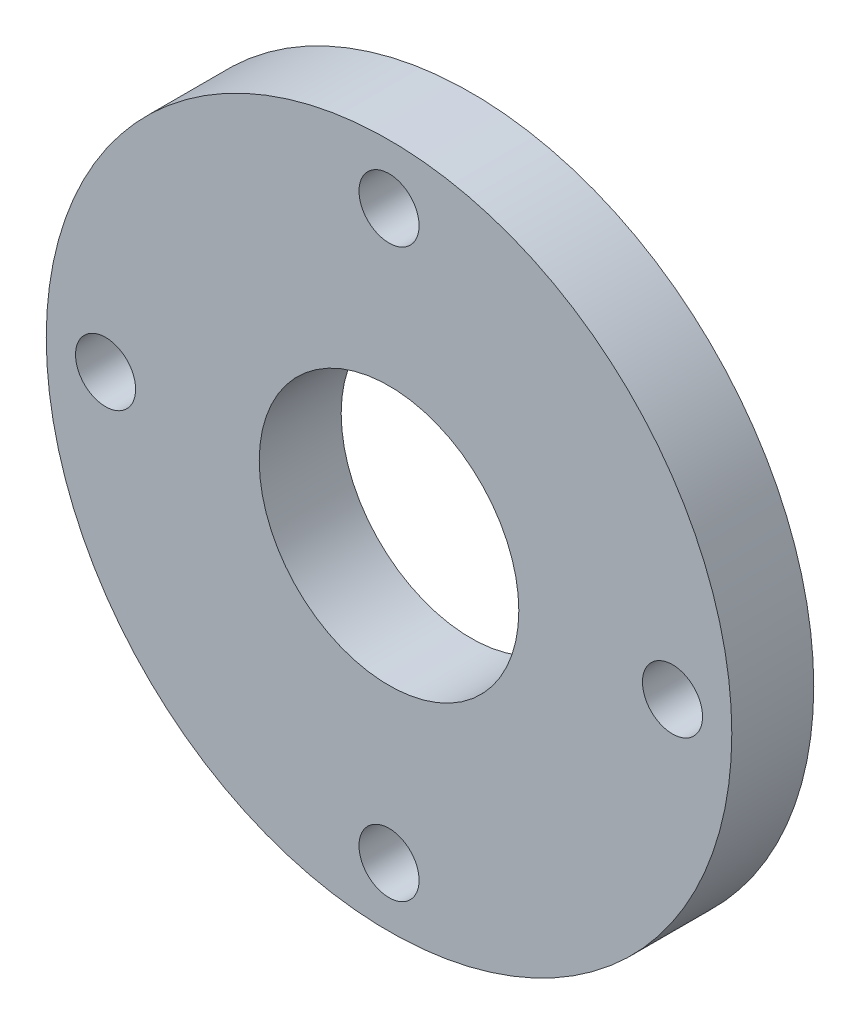
SolidWorks part; units mm, degrees
material "6061-T6 (SS)"
ref_plane "Front Plane" through (0, 0, 0) normal (0, 0, 1) x (1, 0, 0)
ref_plane "Top Plane" through (0, 0, 0) normal (0, 1, 0) x (1, 0, 0)
ref_plane "Right Plane" through (0, 0, 0) normal (1, 0, 0) x (0, 0, -1)
sketch "Sketch1" plane through (0, 0, 0) normal (1, 0, 0) x (0, 0, -1)
  line L0 (-95.847, -9.5) -> (-144, -9.5)
  line L5 (-1000, 0) -> (49000, 0)
  line L6 (0, -9.5) -> (0, 9.5)
  line L13 (0, 9.5) -> (-45.847, 9.5)
  line L26 (-45.847, 9.5) -> (-45.847, 14)
  line L27 (-45.847, 14) -> (-95.847, 14)
  line L32 (-95.847, 14) -> (-95.847, 9.5)
  line L34 (-160, 7) -> (-160, -7)
  line L36 (-95.847, -9.5) -> (-95.847, -14)
  line L37 (-95.847, -14) -> (-45.847, -14)
  line L38 (-45.847, -14) -> (-45.847, -9.5)
  line L39 (0, -9.5) -> (-45.847, -9.5)
  line L40 (-25.305, 37.6491) -> (-16.305, 37.6491)
  line L41 (-111.341, 22.6187) -> (-95.847, 22.6187)
  line L42 (-111.341, 22.6187) -> (-111.341, -22.6187)
  line L43 (-111.341, -22.6187) -> (-95.847, -22.6187)
  line L44 (-95.847, 22.6187) -> (-95.847, -22.6187)
  line L45 (-111.341, 22.6187) -> (-95.847, -22.6187) construction
  line L46 (-111.341, -22.6187) -> (-95.847, 22.6187) construction
  line L47 (-30.353, 22.6187) -> (-45.847, 22.6187)
  line L48 (-30.353, 22.6187) -> (-30.353, -22.6187)
  line L49 (-30.353, -22.6187) -> (-45.847, -22.6187)
  line L50 (-45.847, 22.6187) -> (-45.847, -22.6187)
  line L51 (-30.353, 22.6187) -> (-45.847, -22.6187) construction
  line L52 (-30.353, -22.6187) -> (-45.847, 22.6187) construction
  line L59 (-16.305, 37.6491) -> (-16.305, -37.6491)
  line L60 (-16.305, -37.6491) -> (-25.305, -37.6491)
  line L61 (-25.305, -22.6187) -> (-27.305, -22.6187)
  line L62 (-27.305, -22.6187) -> (-27.305, -12.5)
  line L63 (-27.305, -12.5) -> (-25.305, -12.5)
  line L64 (-25.305, -12.5) -> (-25.305, 12.5)
  line L65 (-25.305, 12.5) -> (-27.305, 12.5)
  line L66 (-27.305, 12.5) -> (-27.305, 22.6187)
  line L67 (-27.305, 22.6187) -> (-25.305, 22.6187)
  line L68 (-25.305, 22.6187) -> (-25.305, 37.6491)
  line L69 (-25.305, -22.6187) -> (-25.305, -37.6491)
  line L71 (-119.469, 37.6491) -> (-26.305, 37.6491)
  line L72 (-119.469, 37.6491) -> (-119.469, -37.6491)
  line L73 (-119.469, -37.6491) -> (-26.305, -37.6491)
  line L74 (-26.305, 37.6491) -> (-26.305, -37.6491)
  line L75 (-119.469, 37.6491) -> (-26.305, -37.6491) construction
  line L76 (-119.469, -37.6491) -> (-26.305, 37.6491) construction
  line L77 (-144, -9.5) -> (-144, -7)
  line L78 (-144, -7) -> (-160, -7)
  line L79 (-95.847, 9.5) -> (-144, 9.5)
  line L80 (-144, 7) -> (-160, 7)
  line L81 (-144, 9.5) -> (-144, 7)
  line L82 (-119.9235, 9.5) -> (-119.9235, -9.5) construction
  line L83 (-22.9235, 9.5) -> (-22.9235, -9.5) construction
  line L96 (-119.469, 37.6491) -> (-128.469, 37.6492)
  line L98 (-119.469, -37.6491) -> (-128.469, -37.6491)
  line L99 (-128.469, 37.6492) -> (-128.469, -37.6491)
  line L110 (-119.469, 37.6491) -> (-119.469, -37.6491)
  point P3 (0, 0)
  point P18 (-103.594, 0)
  point P24 (-38.1, 0)
  point P29 (-72.887, 0)
  point P48 (-16.305, 31.1339)
  point P70 (-128.469, 31.1339)
revolve "Main_body" add sketch "Sketch1" angle 360 about L5 region at (0, 23.5746, 123.969)
sketch "Sketch5" plane through (0, 0, 128.469) normal (0, 0, 1) x (1, 0, 0)
  circle A0 centre (0, 0) radius 14.2558
  dimension "D1" = 28.5115
extrude "seal_seat" cut sketch "Sketch5" against normal through all
hole_wizard "M6 Clearance Hole1" positions "Sketch3" profile "Sketch4" hole size "M6" standard "ANSI Metric" end condition through all
sketch "Sketch3" plane through (0, 0, 128.469) normal (0, 0, 1) x (1, 0, 0)
  point P0 (0, 31.1339)
sketch "Sketch4" plane through (0, 31.1339, 128.469) normal (1, 0, 0) x (0, -1, 0)
  line L0 (0, 0) -> (0, 9)
  line L1 (0, 9) -> (3.3, 9)
  line L2 (3.3, 9) -> (3.3, 0)
  line L5 (3.3, 0) -> (0, 0)
  line L11 (0, -6.35) -> (0, 107.95) construction
  dimension "Thru Hole Dia." = 6.6
  dimension "Thru Hole Depth" = 9
pattern_circular "CirPattern1" count 4 over 360 about axis through (0, 0, 1000) along (0, 0, -1) of "M6 Clearance Hole1"
